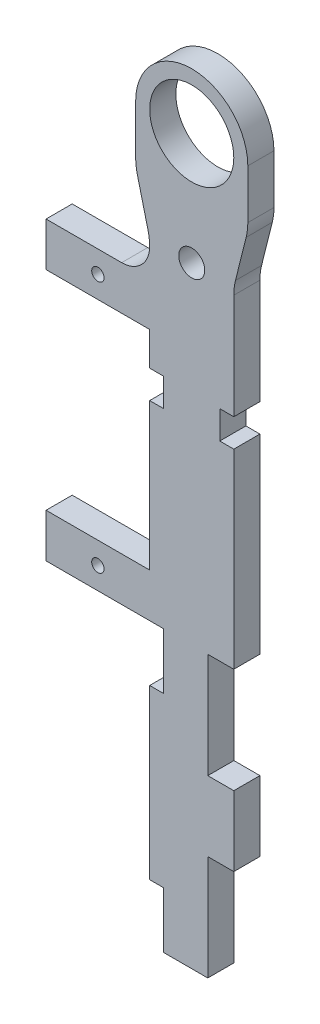
SolidWorks part; units mm, degrees
ref_plane "Front Plane" through (0, 0, 0) normal (0, 0, 1) x (1, 0, 0)
ref_plane "Top Plane" through (0, 0, 0) normal (0, 1, 0) x (1, 0, 0)
ref_plane "Right Plane" through (0, 0, 0) normal (1, 0, 0) x (0, 0, -1)
sketch "Sketch1" plane through (0, 0, 0) normal (0, 0, 1) x (1, 0, 0)
  line L0 (0, 33.02) -> (0, -33.02) construction
  line L1 (4.7625, 33.02) -> (4.7625, -17.145)
  line L2 (-4.7625, 33.02) -> (-4.7625, -17.145)
  line L3 (4.7625, -29.0512) -> (4.7625, -36.9888)
  line L4 (4.7625, -29.0512) -> (1.8161, -29.0513)
  line L5 (4.7625, -36.9888) -> (1.8161, -36.9888)
  line L6 (4.7625, -17.145) -> (1.8161, -17.145)
  line L7 (1.8161, -17.145) -> (1.8161, -29.0513)
  line L8 (4.7625, -33.02) -> (-16.4767, -33.02) construction
  line L9 (-4.7625, -42.545) -> (-3.175, -42.545)
  line L10 (-4.7625, -17.145) -> (-3.175, -17.145)
  line L11 (-3.175, -48.895) -> (-3.175, -42.545)
  line L12 (-4.7625, -23.495) -> (-3.175, -23.495)
  line L13 (-3.175, -17.145) -> (-3.175, -23.495)
  line L14 (-4.7625, -23.495) -> (-4.7625, -42.545)
  line L15 (-3.175, -48.895) -> (1.8161, -48.895)
  line L16 (1.8161, -36.9888) -> (1.8161, -48.895)
  arc A0 (4.7625, 33.02) -> (-4.7625, 33.02) centre (0, 33.02) ccw
  circle A2 centre (0, -21.844) radius 3.175 construction
  circle A3 centre (0, 33.02) radius 3.175
  point P2 (0, 0)
  dimension "D2" = 1.5875
  dimension "D3" = 6.35
  dimension "D4" = 6.35
  dimension "D1" = 66.04
  dimension "D5" = 11.176
  dimension "D6" = 7.9375
  dimension "D7" = 2.9464
  dimension "D8" = 31.75
  dimension "D9" = 1.5875
  dimension "D10" = 6.35
extrude "Boss-Extrude1" add sketch "Sketch1" along normal blind 2.9591
sketch "Sketch2" plane through (0, 0, 2.9591) normal (0, 0, 1) x (1, 0, 0)
  circle A0 centre (0, 20.32) radius 1.5875
  circle A1 centre (0, 33.02) radius 3.175 construction
  dimension "D1" = 3.175
  dimension "D2" = 12.7
sketch "Sketch3" plane through (0, 0, 2.9591) normal (0, 0, 1) x (1, 0, 0)
  line L0 (-4.7625, -17.399) -> (-1.5875, -3.7946) construction
  line L1 (-1.5875, -3.7946) -> (-4.7625, -3.0536) construction
  line L2 (-4.7625, 33.02) -> (-4.7625, -17.145) construction
  line L3 (-4.7625, -3.0536) -> (-7.9375, -16.658) construction
  line L4 (-7.9375, -16.658) -> (-4.7625, -17.399) construction
  line L5 (0, 0) -> (0, -3.8764) construction
  line L6 (7.9375, -16.658) -> (4.7625, -17.399)
  line L7 (4.7625, -3.0536) -> (7.9375, -16.658)
  line L8 (1.5875, -3.7946) -> (4.7625, -3.0536)
  line L9 (4.7625, -17.399) -> (1.5875, -3.7946)
  point P14 (0, -17.399)
  dimension "D1" = 3.175
  dimension "D2" = 13.97
extrude "Cut-Extrude3" [suppressed] cut sketch "Sketch3" against normal up to next contours L8 L7 L6 L9
ref_plane "Plane1" through (0, -17.399, 0) normal (0, 1, 0) x (1, 0, 0)
mirror "Mirror1" [suppressed] about plane through (0, -17.399, 0) normal (0, 1, 0)
chamfer "Chamfer1" [suppressed] distance 6.35 angle 45
sketch "Sketch8" plane through (0, 0, 0) normal (0, 0, -1) x (-1, 0, 0)
  line L0 (-4.7625, -17.145) -> (-4.7625, 33.02) construction
  line L1 (-4.7625, 7.62) -> (-3.175, 7.62)
  line L2 (-4.7625, 7.62) -> (-4.7625, 4.445)
  line L3 (-4.7625, 4.445) -> (-3.175, 4.445)
  line L4 (-3.175, 7.62) -> (-3.175, 4.445)
  line L5 (0, 0) -> (0, 2.5777) construction
  line L6 (3.175, 7.62) -> (3.175, 4.445)
  line L7 (4.7625, 4.445) -> (3.175, 4.445)
  line L8 (4.7625, 7.62) -> (4.7625, 4.445)
  line L9 (4.7625, 7.62) -> (3.175, 7.62)
  circle A0 centre (0, 33.02) radius 3.175 construction
  dimension "D1" = 28.575
  dimension "D2" = 3.175
  dimension "D3" = 1.5875
extrude "Cut-Extrude4" cut sketch "Sketch8" against normal through all
sketch "Sketch4" plane through (0, 0, 2.9591) normal (0, 0, 1) x (1, 0, 0)
  line L0 (-4.7625, 33.02) -> (-4.7625, 7.62) construction
  line L1 (-16.4973, 11.4173) -> (-4.7625, 11.4173)
  line L2 (-16.4973, 11.4173) -> (-16.4973, 16.383)
  line L3 (-16.4973, 16.383) -> (-4.7625, 16.383)
  line L4 (-4.7625, 11.4173) -> (-4.7625, 16.383)
  line L5 (-16.4973, 11.4173) -> (-4.7625, 16.383) construction
  line L6 (-16.4973, 16.383) -> (-4.7625, 11.4173) construction
  line L7 (-17.7625, -0.381) -> (13.2732, -0.381) construction
  line L8 (-10.6299, 11.4173) -> (-10.6299, -12.1793) construction
  line L9 (-16.4973, -17.145) -> (-4.7625, -12.1793) construction
  line L10 (-16.4973, -12.1793) -> (-4.7625, -17.145) construction
  line L11 (-4.7625, -12.1793) -> (-4.7625, -17.145)
  line L12 (-16.4973, -17.145) -> (-4.7625, -17.145)
  line L13 (-16.4973, -12.1793) -> (-16.4973, -17.145)
  line L14 (-16.4973, -12.1793) -> (-4.7625, -12.1793)
  line L15 (-4.7625, 4.445) -> (-4.7625, -17.145) construction
  line L16 (-4.7625, -17.145) -> (-3.175, -17.145) construction
  circle A0 centre (-10.6299, 13.9001) radius 1.016 construction
  circle A2 centre (-10.6299, -14.6621) radius 1.016 construction
  dimension "D1" = 2.032
  dimension "D2" = 11.7348
  dimension "D3" = 23.5966
  dimension "D4" = 33.528
extrude "Boss-Extrude2" add sketch "Sketch4" against normal up to surface (2.9591 mm away) up to face at (-0.2265, -12.9778, 0)
fillet "Fillet1" radius 3.175 1 edges at (-4.7625, 16.383, 1.4796)
hole_wizard "#0 Clearance Hole1" positions "Sketch6" profile "Sketch7" hole size "#0" standard "ANSI Inch" end condition through all
sketch "Sketch6" plane through (0, 0, 0) normal (0, 0, -1) x (-1, 0, 0)
  point P0 (10.6299, 13.9001)
  point P3 (10.6299, -14.6621)
sketch "Sketch7" plane through (-10.6299, 13.9001, 0) normal (1, 0, 0) x (0, 1, 0)
  line L0 (0, 0) -> (0, 2.9591)
  line L1 (0, 2.9591) -> (0.6985, 2.9591)
  line L2 (0.6985, 2.9591) -> (0.6985, 0)
  line L5 (0.6985, 0) -> (0, 0)
  line L11 (0, -6.35) -> (0, 107.95) construction
  dimension "Thru Hole Dia." = 1.397
  dimension "Thru Hole Depth" = 2.9591
hole_wizard "#4 Clearance Hole1" positions "Sketch10" profile "Sketch9" hole size "#4" standard "ANSI Inch" end condition through all
sketch "Sketch10" plane through (0, 0, 2.9591) normal (0, 0, 1) x (1, 0, 0)
  point P0 (0, 20.32)
sketch "Sketch9" plane through (0, 20.32, 2.9591) normal (1, 0, 0) x (0, -1, 0)
  line L0 (0, 0) -> (0, 2.9591)
  line L1 (0, 2.9591) -> (1.4732, 2.9591)
  line L2 (1.4732, 2.9591) -> (1.4732, 0)
  line L5 (1.4732, 0) -> (0, 0)
  line L11 (0, -6.35) -> (0, 107.95) construction
  dimension "Thru Hole Dia." = 2.9464
  dimension "Thru Hole Depth" = 2.9591
sketch "Sketch11" plane through (0, 0, 2.9591) normal (0, 0, 1) x (1, 0, 0)
  line L0 (-6.35, 33.02) -> (-6.35, 26.67)
  line L1 (6.35, 33.02) -> (6.35, 26.67)
  line L2 (-6.35, 26.67) -> (-4.7625, 20.32)
  line L3 (-4.7625, 33.02) -> (-4.7625, 19.558) construction
  line L4 (4.7625, 20.32) -> (6.35, 26.67)
  line L5 (4.7625, 7.62) -> (4.7625, 33.02) construction
  line L6 (4.7625, 20.32) -> (4.7625, 33.02)
  line L7 (-4.7625, 33.02) -> (-4.7625, 20.32)
  arc A0 (6.35, 33.02) -> (-6.35, 33.02) centre (0, 33.02) ccw
  circle A1 centre (0, 33.02) radius 3.175 construction
  arc A2 (4.7625, 33.02) -> (-4.7625, 33.02) centre (0, 33.02) ccw construction
  arc A3 (4.7625, 33.02) -> (-4.7625, 33.02) centre (0, 33.02) ccw
  dimension "D1" = 3.175
  dimension "D2" = 6.35
  dimension "D3" = 6.35
extrude "Boss-Extrude3" add sketch "Sketch11" against normal up to surface (2.9591 mm away) up to face at (1.4732, 20.32, 0)
fillet "Fillet2" radius 6.35 4 edges at (4.7625, 20.32, 1.4796) (6.35, 26.67, 1.4796) (-6.35, 26.67, 1.4796) (-4.7625, 20.32, 1.4796)
sketch "Sketch12" plane through (0, 0, 2.9591) normal (0, 0, 1) x (1, 0, 0)
  circle A0 centre (0, 33.02) radius 4.7625
  dimension "D1" = 9.525
extrude "Cut-Extrude5" cut sketch "Sketch12" against normal up to next
